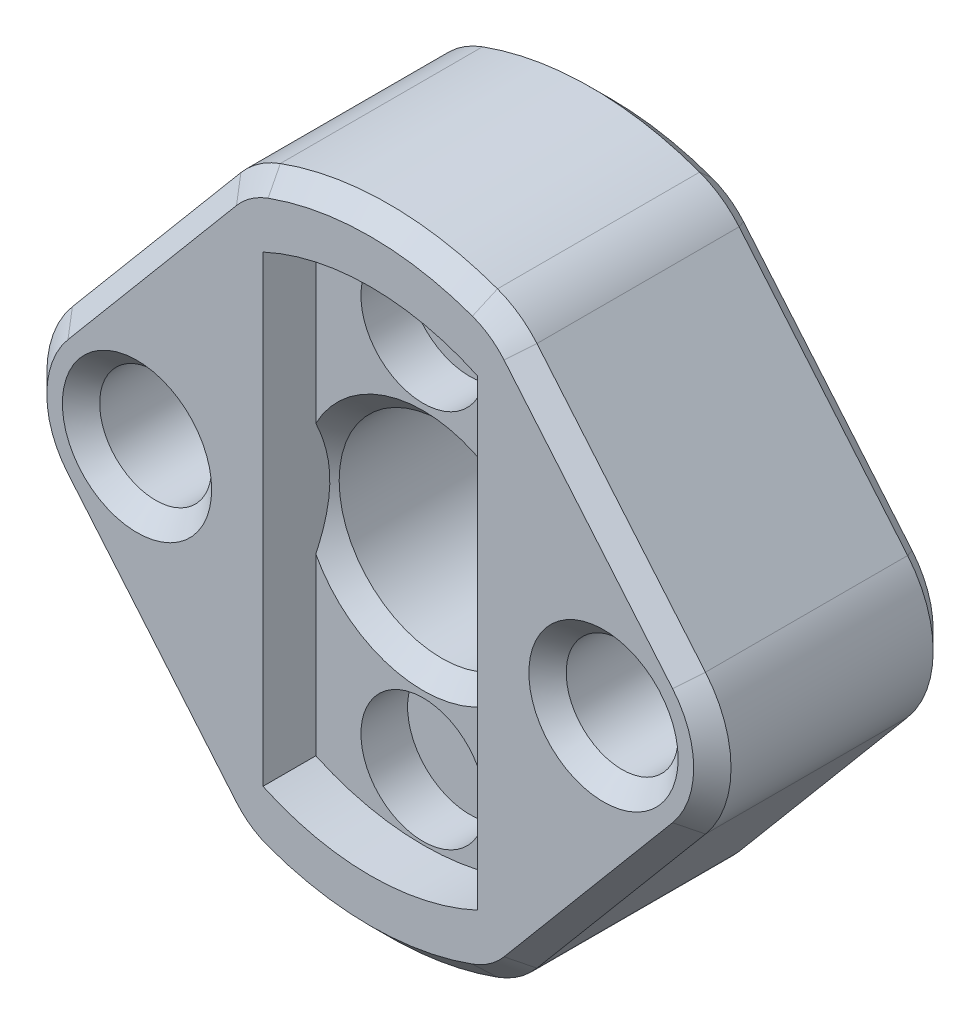
SolidWorks part; units mm, degrees
ref_plane "Top Plane" through (0, 0, 0) normal (0, 0, 1) x (1, 0, 0)
ref_plane "Right Plane" through (0, 0, 0) normal (0, 1, 0) x (1, 0, 0)
ref_plane "Front Plane" through (0, 0, 0) normal (1, 0, 0) x (0, 0, -1)
sketch "Sketch1" plane through (0, 0, 0) normal (0, 0, 1) x (1, 0, 0)
  line L0 (-3.25, 7.3101) -> (-3.25, -7.3101) construction
  line L1 (3.25, 7.3101) -> (3.25, -7.3101) construction
  line L2 (-3.45, 7.4389) -> (-3.45, -7.4389)
  line L3 (3.45, 7.4389) -> (3.45, -7.4389)
  line L4 (-4.2915, 9.2533) -> (-10.1787, 2.2527)
  line L5 (-4.2915, -9.2533) -> (-10.1787, -2.2527)
  line L6 (4.2915, -9.2533) -> (10.1787, -2.2527)
  line L7 (4.2915, 9.2533) -> (10.1787, 2.2527)
  circle A0 centre (7.5, 0) radius 1.8 construction
  circle A1 centre (-7.5, 0) radius 1.8 construction
  circle A2 centre (7.5, 0) radius 1.8
  circle A3 centre (-7.5, 0) radius 1.8
  arc A4 (3.25, 7.3101) -> (-3.25, 7.3101) centre (0, 0) ccw construction
  arc A5 (3.25, 7.3101) -> (-3.25, 7.3101) centre (0, 0) ccw construction
  arc A6 (-3.25, -7.3101) -> (3.25, -7.3101) centre (0, 0) ccw construction
  arc A7 (-3.25, -7.3101) -> (3.25, -7.3101) centre (0, 0) ccw construction
  arc A8 (3.45, 7.4389) -> (-3.45, 7.4389) centre (0, 0) ccw
  arc A9 (-3.45, -7.4389) -> (3.45, -7.4389) centre (0, 0) ccw
  arc A10 (4.2915, 9.2533) -> (-4.2915, 9.2533) centre (0, 0) ccw
  arc A11 (-4.2915, -9.2533) -> (4.2915, -9.2533) centre (0, 0) ccw
  arc A12 (-10.1787, 2.2527) -> (-10.1787, -2.2527) centre (-7.5, 0) ccw
  arc A13 (10.1787, -2.2527) -> (10.1787, 2.2527) centre (7.5, 0) ccw
  dimension "D3" = 7
  dimension "D1" = 0.2
  dimension "D2" = 2
extrude "Boss-Extrude1" add sketch "Sketch1" against normal blind 1.7
sketch "Sketch2" plane through (0, 0, -1.7) normal (0, 0, -1) x (-1, 0, 0)
  line L0 (4.2915, 9.2533) -> (10.1787, 2.2527) construction
  line L1 (10.1787, -2.2527) -> (4.2915, -9.2533) construction
  line L2 (-4.2915, -9.2533) -> (-10.1787, -2.2527) construction
  line L3 (-10.1787, 2.2527) -> (-4.2915, 9.2533) construction
  line L4 (4.2915, 9.2533) -> (10.1787, 2.2527)
  line L5 (10.1787, -2.2527) -> (4.2915, -9.2533)
  line L6 (-4.2915, -9.2533) -> (-10.1787, -2.2527)
  line L7 (-10.1787, 2.2527) -> (-4.2915, 9.2533)
  circle A0 centre (0, 0) radius 3.3
  arc A1 (10.1787, -2.2527) -> (10.1787, 2.2527) centre (7.5, 0) ccw construction
  arc A2 (-4.2915, -9.2533) -> (4.2915, -9.2533) centre (0, 0) ccw construction
  arc A3 (-10.1787, 2.2527) -> (-10.1787, -2.2527) centre (-7.5, 0) ccw construction
  arc A4 (4.2915, 9.2533) -> (-4.2915, 9.2533) centre (0, 0) ccw construction
  arc A5 (10.1787, -2.2527) -> (10.1787, 2.2527) centre (7.5, 0) ccw
  arc A6 (-4.2915, -9.2533) -> (4.2915, -9.2533) centre (0, 0) ccw
  arc A7 (-10.1787, 2.2527) -> (-10.1787, -2.2527) centre (-7.5, 0) ccw
  arc A8 (4.2915, 9.2533) -> (-4.2915, 9.2533) centre (0, 0) ccw
  line M9 (-3.45, -7.4389) -> (-3.45, 7.4389)
  arc M10 (-3.45, 7.4389) -> (3.45, 7.4389) centre (0, 0) cw
  line M11 (3.45, 7.4389) -> (3.45, -7.4389)
  arc M12 (3.45, -7.4389) -> (-3.45, -7.4389) centre (0, 0) cw
  circle M13 centre (7.5, 0) radius 1.8
  circle M14 centre (-7.5, 0) radius 1.8
  arc M15 (4.2915, 9.2533) -> (-4.2915, 9.2533) centre (0, 0) ccw
  line M16 (-4.2915, 9.2533) -> (-10.1787, 2.2527)
  arc M17 (-10.1787, 2.2527) -> (-10.1787, -2.2527) centre (-7.5, 0) ccw
  line M18 (-10.1787, -2.2527) -> (-4.2915, -9.2533)
  arc M19 (-4.2915, -9.2533) -> (4.2915, -9.2533) centre (0, 0) ccw
  line M20 (4.2915, -9.2533) -> (10.1787, -2.2527)
  arc M21 (10.1787, -2.2527) -> (10.1787, 2.2527) centre (7.5, 0) ccw
  line M22 (10.1787, 2.2527) -> (4.2915, 9.2533)
  dimension "D1" = 6.6
extrude "Boss-Extrude2" add sketch "Sketch2" along normal blind 6 contours M22 M15 M16 M17 M18 M19 M20 M21 M14 M13 M12 M9 M10 M11 | A0 M9 M12 M11 M10 region at (-7.0055, 5.5599, -1.7) region at (3.4322, 0, -1.7)
fillet "Fillet1" radius 3 4 edges at (-4.2915, 9.2533, -3.85) (4.2915, 9.2533, -3.85) (-4.2915, -9.2533, -3.85) (4.2915, -9.2533, -3.85)
chamfer "Chamfer1" distance 0.6 angle 45 14 edges at (7.4694, -5.4744, -7.7) (4.1836, -9.2235, -7.7) (11, 0, -7.7) (0, -10.2, -7.7) (7.4694, 5.4744, -7.7) (-4.1836, -9.2235, -7.7) (4.1836, 9.2235, -7.7) (-7.4694, -5.4744, -7.7) (0, 10.2, -7.7) (-11, 0, -7.7) (-4.1836, 9.2235, -7.7) (-7.4694, 5.4744, -7.7) (-3.3, 0, -7.7) (-3.3, 0, -1.7)
chamfer "Chamfer2" distance 0.6 angle 45 2 edges at (-9.3, 0, -7.7) (5.7, 0, -7.7)
chamfer "Chamfer3" distance 0.6 angle 45 12 edges at (7.4694, 5.4744, 0) (4.1836, 9.2235, 0) (11, 0, 0) (0, 10.2, 0) (7.4694, -5.4744, 0) (-4.1836, 9.2235, 0) (4.1836, -9.2235, 0) (-7.4694, 5.4744, 0) (0, -10.2, 0) (-11, 0, 0) (-4.1836, -9.2235, 0) (-7.4694, -5.4744, 0)
chamfer "Chamfer4" distance 0.6 angle 45 2 edges at (-5.7, 0, 0) (9.3, 0, 0)
sketch "Sketch4" plane through (0, 0, -1.7) normal (0, 0, 1) x (1, 0, 0)
  circle A0 centre (0, 6.1) radius 2
  circle A1 centre (0, -6.1) radius 2
  dimension "D1" = 4
extrude "Cut-Extrude1" cut sketch "Sketch4" against normal blind 1.5 contours A1 | A0
